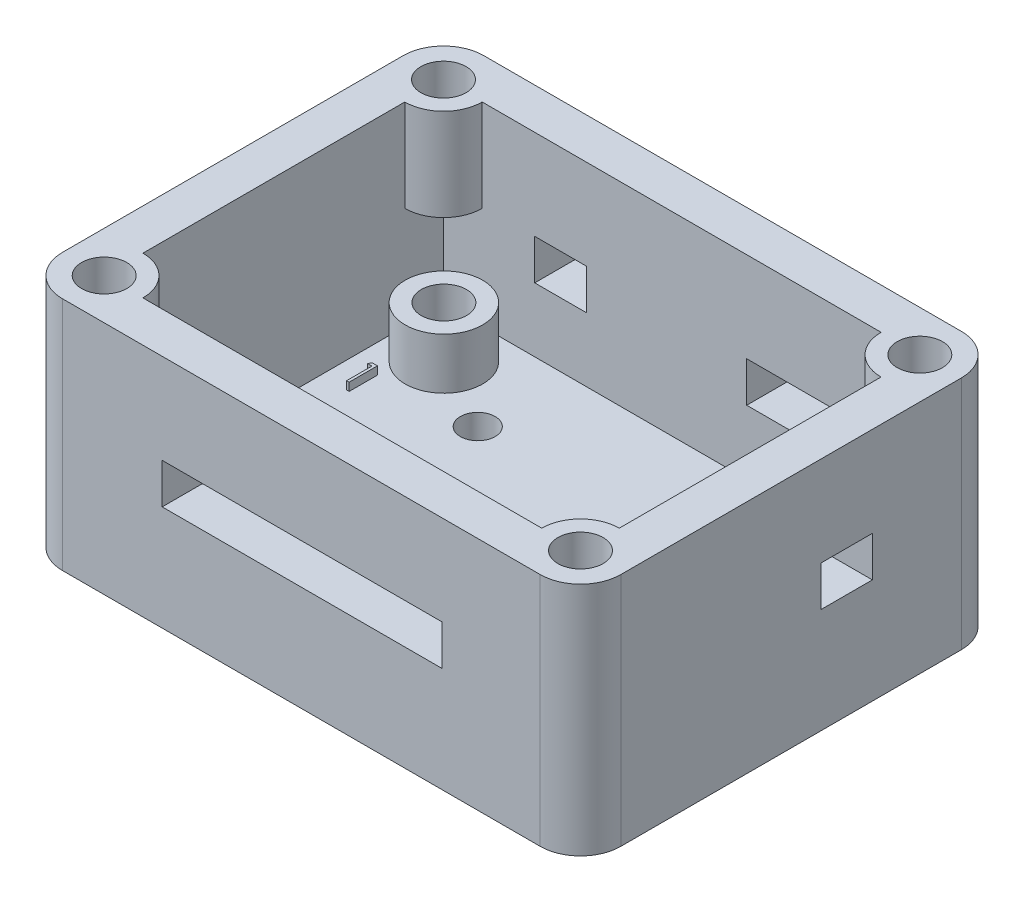
SolidWorks part; units mm, degrees
ref_plane "Front Plane" through (0, 0, 0) normal (0, 0, 1) x (1, 0, 0)
ref_plane "Top Plane" through (0, 0, 0) normal (0, 1, 0) x (1, 0, 0)
ref_plane "Right Plane" through (0, 0, 0) normal (1, 0, 0) x (0, 0, -1)
sketch "Sketch1" plane through (0, 0, 0) normal (0, 1, 0) x (1, 0, 0)
  line L1 (-34.63, -26.13) -> (34.63, -26.13)
  line L2 (-34.63, -26.13) -> (-34.63, 26.13)
  line L3 (-34.63, 26.13) -> (34.63, 26.13)
  line L4 (34.63, -26.13) -> (34.63, 26.13)
  line L5 (-34.63, -26.13) -> (34.63, 26.13) construction
  line L6 (-34.63, 26.13) -> (34.63, -26.13) construction
  point P0 (0, 0)
  dimension "Outer Box Length" = 69.26
  dimension "Outer Box Width" = 52.26
extrude "Boss-Extrude3" add sketch "Sketch1" along normal blind 29.208 contours L3 L4 L1 L2
sketch "Sketch2" plane through (0, 29.208, 0) normal (0, 1, 0) x (1, 0, 0)
  line L0 (-34.63, 26.13) -> (34.63, 26.13) construction
  line L1 (29.55, -21.05) -> (-29.55, -21.05)
  line L2 (29.55, -21.05) -> (29.55, 21.05)
  line L3 (29.55, 21.05) -> (-29.55, 21.05)
  line L4 (-29.55, -21.05) -> (-29.55, 21.05)
  line L5 (29.55, -21.05) -> (-29.55, 21.05) construction
  line L6 (29.55, 21.05) -> (-29.55, -21.05) construction
  line L7 (-34.63, -26.13) -> (-34.63, 26.13) construction
  point P0 (0, 0)
  dimension "D1" = 5.08
  dimension "D2" = 5.08
extrude "Cut-Extrude4" cut sketch "Sketch2" against normal blind 24.128 contours L4 L3 L2 L1
fillet "Fillet1" radius 5 4 edges at (34.63, 14.604, -26.13) (-34.63, 14.604, -26.13) (-34.63, 14.604, 26.13) (34.63, 14.604, 26.13)
sketch "Sketch3" plane through (0, 29.208, 0) normal (0, 1, 0) x (1, 0, 0)
  circle A0 centre (-29.55, 21.05) radius 4.8067
  circle A2 centre (29.55, 21.05) radius 4.8067
  circle A3 centre (-29.55, -21.05) radius 4.8067
  circle A4 centre (29.55, -21.05) radius 4.8067
  circle A5 centre (-29.55, 21.05) radius 2.8067
  circle A6 centre (29.55, 21.05) radius 2.8067
  circle A7 centre (29.55, -21.05) radius 2.8067
  circle A8 centre (-29.55, -21.05) radius 2.8067
  dimension "D1" = 9.6134
extrude "Boss-Extrude4" add sketch "Sketch3" against normal blind 11.43 contours A2 | A0 | A3 | A4
extrude "Cut-Extrude5" cut sketch "Sketch3<3>" against normal blind 6.35 contours A5 | A8 | A7 | A6
sketch "Sketch3<3>" plane through (0, 29.208, 0) normal (0, 1, 0) x (1, 0, 0) same geometry as "Sketch3"
sketch "Sketch9" plane through (0, 5.08, 0) normal (0, 1, 0) x (1, 0, 0)
  line L0 (-29.55, -16.2433) -> (-29.55, 16.2433) construction
  line L1 (29.55, 21.05) -> (-29.55, 21.05) construction
  line L2 (29.55, -21.05) -> (29.55, 21.05) construction
  line L3 (29.55, -21.05) -> (-29.55, -21.05) construction
  line L4 (-29.55, -21.05) -> (-29.55, 21.05) construction
  circle A0 centre (-23.35, 14.9) radius 4.8067
  circle A1 centre (23.65, 15.15) radius 4.8067
  circle A2 centre (23.4, -15.1) radius 4.8067
  circle A3 centre (-23.6, -15.1) radius 4.8067
  circle A4 centre (-23.6, -15.1) radius 2.8067
  circle A5 centre (23.4, -15.1) radius 2.8067
  circle A6 centre (23.65, 15.15) radius 2.8067
  circle A7 centre (-23.35, 14.9) radius 2.8067
  dimension "D3" = 9.6134
  dimension "D1" = 6.2
  dimension "D2" = 6.15
  dimension "D4" = 5.9
  dimension "D5" = 5.9
  dimension "D6" = 6.15
  dimension "D7" = 5.95
  dimension "D8" = 5.95
  dimension "D9" = 5.95
  dimension "D10" = 2
extrude "Boss-Extrude5" add sketch "Sketch9" along normal blind 6.35
sketch "Sketch10" plane through (0, 5.08, 0) normal (0, 1, 0) x (1, 0, 0)
  line L1 (-14.275, -10.025) -> (14.275, -10.025)
  line L2 (-14.275, -10.025) -> (-14.275, 10.025)
  line L3 (-14.275, 10.025) -> (14.275, 10.025)
  line L4 (14.275, -10.025) -> (14.275, 10.025)
  line L5 (-14.275, -10.025) -> (14.275, 10.025) construction
  line L6 (-14.275, 10.025) -> (14.275, -10.025) construction
  circle A0 centre (14.275, 10.025) radius 2.159
  circle A1 centre (14.275, -10.025) radius 2.159
  circle A2 centre (-14.275, 10.025) radius 2.159
  circle A3 centre (-14.275, -10.025) radius 2.159
  point P0 (0, 0)
  dimension "D3" = 4.318
  dimension "D1" = 28.55
  dimension "D2" = 20.05
extrude "Cut-Extrude6" cut sketch "Sketch10" against normal up to surface (5.08 mm away) contours A0 | A1 | A3 | A2 up to face at (0, 0, 0)
sketch "Sketch12" plane through (0, 5.08, 0) normal (0, 1, 0) x (1, 0, 0)
  line L0 (-29.55, -21.05) -> (-29.55, 21.05) construction
  circle A0 centre (-23.35, 14.9) radius 4.8067 construction
  text T0 "1"
  dimension "D1" = 2
  dimension "D2" = 10
extrude "Boss-Extrude6" add sketch "Sketch12" along normal blind 1
sketch "Face 1 Connector Holes" plane through (-34.63, 0, 0) normal (-1, 0, 0) x (0, 0, 1)
  line L0 (-21.13, 29.208) -> (-21.13, 0) construction
  line L1 (-21.13, 29.03) -> (21.13, 29.03)
  line L2 (-21.13, 29.03) -> (-21.13, 13.03)
  line L3 (-21.13, 13.03) -> (21.13, 13.03)
  line L4 (21.13, 29.03) -> (21.13, 13.03)
  line L5 (21.13, 0) -> (21.13, 29.208) construction
  line L6 (21.13, 0) -> (-21.13, 0) construction
  dimension "D1" = 16
  dimension "D2" = 13.03
sketch "Face 2 Connector Holes" plane through (0, 0, -26.13) normal (0, 0, -1) x (-1, 0, 0)
  line L0 (29.63, 0) -> (29.63, 29.208) construction
  line L1 (29.63, 13.03) -> (-29.63, 13.03)
  line L2 (29.63, 13.03) -> (29.63, 29.03)
  line L3 (29.63, 29.03) -> (-29.63, 29.03)
  line L4 (-29.63, 13.03) -> (-29.63, 29.03)
  line L5 (-29.63, 29.208) -> (-29.63, 0) construction
  line L6 (29.63, 0) -> (-29.63, 0) construction
  line L8 (18.23, 13.03) -> (11.83, 13.03)
  line L9 (18.23, 13.03) -> (18.23, 18.03)
  line L10 (18.23, 18.03) -> (11.83, 18.03)
  line L11 (11.83, 13.03) -> (11.83, 18.03)
  line L12 (-8.07, 13.03) -> (-18.47, 13.03)
  line L13 (-8.07, 13.03) -> (-8.07, 18.03)
  line L14 (-8.07, 18.03) -> (-18.47, 18.03)
  line L15 (-18.47, 13.03) -> (-18.47, 18.03)
  dimension "D1" = 13.03
  dimension "D2" = 16
  dimension "D3" = 11.4
  dimension "D4" = 6.4
  dimension "D5" = 5
  dimension "D6" = 37.7
  dimension "D7" = 10.4
  dimension "D8" = 5
extrude "Cut-Extrude7" cut sketch "Face 2 Connector Holes" against normal up to surface (5.08 mm away) contours L14 L15 L12 L13 | L10 L11 L8 L9 up to face at (0, 17.461, -21.05)
sketch "Face 3 Connector Holes" plane through (34.63, 0, 0) normal (1, 0, 0) x (0, 0, -1)
  line L0 (-21.13, 29.208) -> (-21.13, 0) construction
  line L1 (-21.13, 29.03) -> (21.13, 29.03)
  line L2 (-21.13, 29.03) -> (-21.13, 13.03)
  line L3 (-21.13, 13.03) -> (21.13, 13.03)
  line L4 (21.13, 29.03) -> (21.13, 13.03)
  line L5 (21.13, 0) -> (21.13, 29.208) construction
  line L6 (-21.13, 0) -> (21.13, 0) construction
  line L8 (3.68, 13.03) -> (10.08, 13.03)
  line L9 (3.68, 13.03) -> (3.68, 18.03)
  line L10 (3.68, 18.03) -> (10.08, 18.03)
  line L11 (10.08, 13.03) -> (10.08, 18.03)
  dimension "D4" = 6.4
  dimension "D5" = 5
  dimension "D1" = 16
  dimension "D2" = 13.03
  dimension "D3" = 11.05
sketch "Face 4 Connector Holes" plane through (0, 0, 26.13) normal (0, 0, 1) x (1, 0, 0)
  line L0 (-29.63, 29.208) -> (-29.63, 0) construction
  line L1 (-29.63, 29.03) -> (29.63, 29.03)
  line L2 (-29.63, 29.03) -> (-29.63, 13.03)
  line L3 (-29.63, 13.03) -> (29.63, 13.03)
  line L4 (29.63, 29.03) -> (29.63, 13.03)
  line L5 (29.63, 0) -> (29.63, 29.208) construction
  line L6 (-29.63, 0) -> (29.63, 0) construction
  line L8 (-17.27, 13.03) -> (17.43, 13.03)
  line L9 (-17.27, 13.03) -> (-17.27, 18.03)
  line L10 (-17.27, 18.03) -> (17.43, 18.03)
  line L11 (17.43, 13.03) -> (17.43, 18.03)
  dimension "D1" = 16
  dimension "D2" = 13.03
  dimension "D3" = 34.7
  dimension "D4" = 5
  dimension "D5" = 12.2
extrude "Cut-Extrude8" cut sketch "Face 3 Connector Holes" against normal up to surface (5.08 mm away) contours L10 L11 L8 L9 up to face at (29.55, 17.461, 0)
extrude "Cut-Extrude9" cut sketch "Face 4 Connector Holes" against normal blind 5.08 contours L10 L11 L8 L9
equation "\"PCB Length\"= 57.1mm"
equation "\"PCB Width\"= 40.1mm"
equation "\"PCB Height\"= 16mm"
equation "\"Insert Height\"= 0.25in"
equation "\"Wall Thickness\"= 0.2in"
equation "\"Support Hole OD\"= 0.17in"
equation "\"PCB Margin\"= 1mm"
equation "\"Screw Length\"= 7in / 16"
equation "\"Insert OD Size\"= 0.221in"
equation "\"PCB d1\"= 5.2mm"
equation "\"PCB d2\"= 5.15mm"
equation "\"PCB d3\"= 4.9mm"
equation "\"PCB d4\"= 4.9mm"
equation "\"PCB d5\"= 5.15mm"
equation "\"PCB d6\"= 4.95mm"
equation "\"PCB d7\"= 4.95mm"
equation "\"PCB d8\"= 4.95mm"
equation "\"Insert Wall Thickness\"= 2mm"
equation "\"PCB Underside Washer\"= 0.07in"
equation "\"Outer Box Length@Sketch1\" = 2 * \"Wall Thickness\" + 2 * \"PCB Margin\" + \"PCB Length\""
equation "\"Outer Box Width@Sketch1\"=2 * \"Wall Thickness\" + 2 * \"PCB Margin\" + \"PCB Width\""
equation "\"D1@Boss-Extrude3\"=\"Wall Thickness\"+\"Insert Height\"+\"PCB Underside Washer\"+\"PCB Height\""
equation "\"D2@Sketch2\"=\"Wall Thickness\""
equation "\"D1@Sketch2\"=\"Wall Thickness\" "
equation "\"D1@Cut-Extrude4\"=\"PCB Height\"+\"PCB Underside Washer\"+\"Insert Height\""
equation "\"D1@Sketch3\"=\"Insert OD Size\"+ 2 * \"Insert Wall Thickness\""
equation "\"D1@Boss-Extrude4\"=\"Insert Height\"+ \"Wall Thickness\""
equation "\"D1@Cut-Extrude5\"=\"Insert Height\""
equation "\"D1@Sketch9\"=\"PCB d1\" + \"PCB Margin\""
equation "\"D4@Sketch9\"=\"PCB d3\"+\"PCB Margin\""
equation "\"D5@Sketch9\"=\"PCB d4\"+\"PCB Margin\""
equation "\"D6@Sketch9\"=\"PCB d5\" + \"PCB Margin\""
equation "\"D2@Sketch9\"=\"PCB d2\" + \"PCB Margin\" "
equation "\"D7@Sketch9\"=\"PCB d6\"+\"PCB Margin\""
equation "\"D8@Sketch9\"= \"PCB d8\"+\"PCB Margin\""
equation "\"D9@Sketch9\"=\"PCB d7\"+\"PCB Margin\""
equation "\"D10@Sketch9\"=\"Insert Wall Thickness\""
equation "\"D1@Boss-Extrude5\"=\"Insert Height\""
equation "\"D1@Sketch10\"=\"PCB Length\"/2"
equation "\"D2@Sketch10\"=\"PCB Width\"/2"
equation "\"D3@Sketch10\"=\"Support Hole OD\""
equation "\"D3@Sketch9\"=\"Insert OD Size\" + 2 * \"Insert Wall Thickness\""
equation "\"D1@Face 2 Connector Holes\"=\"Wall Thickness\" + \"Insert Height\"+1.6mm"
equation "\"D2@Face 2 Connector Holes\" = \"PCB Height\""
equation "\"D1@Face 1 Connector Holes\" = \"PCB Height\""
equation "\"D2@Face 1 Connector Holes\"=\"Wall Thickness\" +\"Insert Height\"+ 1.6mm"
equation "\"D1@Face 3 Connector Holes\" = \"PCB Height\""
equation "\"D2@Face 3 Connector Holes\"=\"Wall Thickness\" +\"Insert Height\"+ 1.6mm"
equation "\"D1@Face 4 Connector Holes\" = \"PCB Height\""
equation "\"D2@Face 4 Connector Holes\"=\"Wall Thickness\" +\"Insert Height\"+ 1.6mm"
equation "\"D6@Face 2 Connector Holes\"=36.7mm + \"PCB Margin\""
equation "\"D3@Face 2 Connector Holes\"=10.4mm + \"PCB Margin\""
equation "\"D3@Face 3 Connector Holes\"=10.05mm + \"PCB Margin\""
equation "\"D5@Face 4 Connector Holes\"=11.2mm + \"PCB Margin\""
